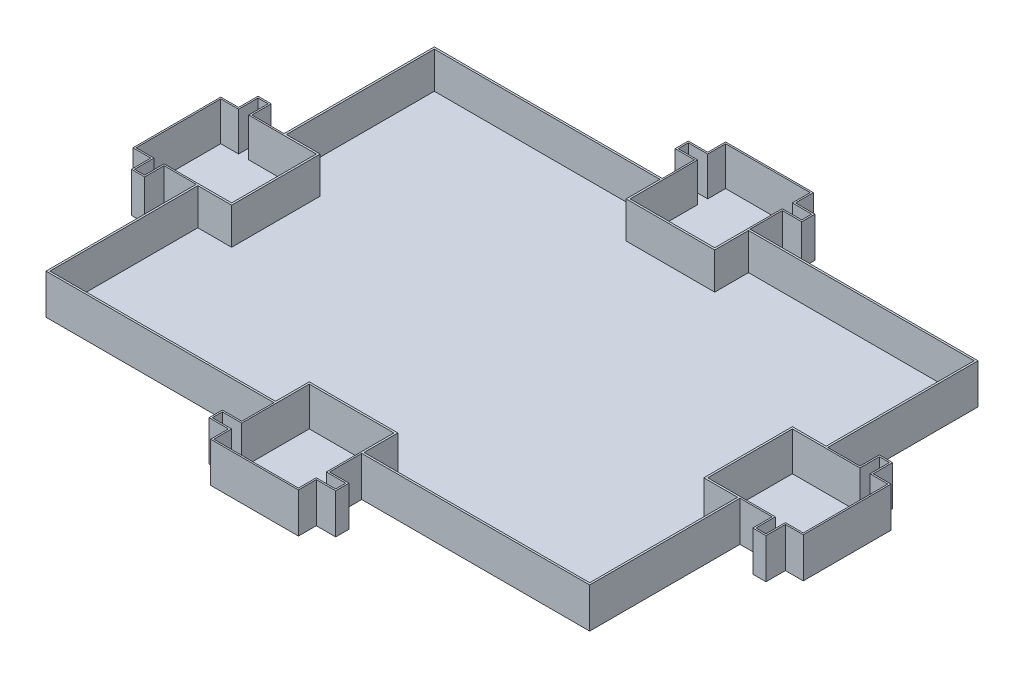
SolidWorks part; units mm, degrees
ref_plane "Alzado" through (0, 0, 0) normal (0, 0, 1) x (1, 0, 0)
ref_plane "Planta" through (0, 0, 0) normal (0, 1, 0) x (1, 0, 0)
ref_plane "Vista lateral" through (0, 0, 0) normal (1, 0, 0) x (0, 0, -1)
sketch "Croquis1" plane through (0, 0, 0) normal (0, 1, 0) x (1, 0, 0)
  line L0 (-10.9, -41.3) -> (10.9, -41.3)
  line L1 (70, -50) -> (-70, -50)
  line L2 (70, -50) -> (70, -10.9)
  line L3 (70, 50) -> (10.9, 50)
  line L4 (-70, -50) -> (-70, 50)
  line L5 (70, -50) -> (-70, 50) construction
  line L6 (70, 50) -> (-70, -50) construction
  line L11 (70, 10.9) -> (70, 50)
  line L12 (-78.3, 16.3) -> (-81.7, 16.3)
  line L13 (-10.9, -41.3) -> (-10.9, -58.7)
  line L15 (10.9, -41.3) -> (10.9, -58.7)
  line L16 (-81.7, 11.3) -> (-81.7, 16.3)
  line L17 (-81.7, 11.3) -> (-86.3, 11.3)
  line L19 (-10.9, 58.7) -> (-10.9, 41.3)
  line L20 (-10.9, 41.3) -> (10.9, 41.3)
  line L21 (10.9, 58.7) -> (10.9, 41.3)
  line L22 (-11.3, 58.3) -> (-11.3, 40.9)
  line L23 (-11.3, 40.9) -> (11.3, 40.9)
  line L24 (61.3, -10.9) -> (61.3, 10.9)
  line L25 (61.3, -10.9) -> (78.7, -10.9)
  line L27 (61.3, 10.9) -> (78.7, 10.9)
  line L28 (-86.3, 11.3) -> (-86.3, -11.3)
  line L29 (-81.7, -11.3) -> (-86.3, -11.3)
  line L32 (-10.9, -61.3) -> (-10.9, -65.9)
  line L33 (-10.9, -65.9) -> (10.9, -65.9)
  line L34 (10.9, -61.3) -> (10.9, -65.9)
  line L35 (-10.9, -58.7) -> (-15.9, -58.7)
  line L37 (-10.9, -61.3) -> (-15.9, -61.3)
  line L38 (-15.9, -58.7) -> (-15.9, -61.3)
  line L39 (10.9, -58.7) -> (15.9, -58.7)
  line L41 (10.9, -61.3) -> (15.9, -61.3)
  line L42 (15.9, -58.7) -> (15.9, -61.3)
  line L43 (0, 30.1645) -> (0, -22.5946)
  line L45 (-10.9, 61.3) -> (-10.9, 65.9)
  line L46 (-10.9, 65.9) -> (10.9, 65.9)
  line L47 (10.9, 61.3) -> (10.9, 65.9)
  line L48 (10.9, 58.7) -> (15.9, 58.7)
  line L50 (10.9, 61.3) -> (15.9, 61.3)
  line L51 (15.9, 58.7) -> (15.9, 61.3)
  line L52 (-10.9, 58.7) -> (-15.9, 58.7)
  line L54 (-10.9, 61.3) -> (-15.9, 61.3)
  line L55 (-15.9, 58.7) -> (-15.9, 61.3)
  line L56 (81.3, 10.9) -> (85.9, 10.9)
  line L58 (81.3, -10.9) -> (85.9, -10.9)
  line L59 (85.9, 10.9) -> (85.9, -10.9)
  line L61 (78.7, 10.9) -> (78.7, 15.9)
  line L62 (78.7, 15.9) -> (81.3, 15.9)
  line L63 (81.3, 10.9) -> (81.3, 15.9)
  line L65 (78.7, -10.9) -> (78.7, -15.9)
  line L66 (78.7, -15.9) -> (81.3, -15.9)
  line L67 (81.3, -10.9) -> (81.3, -15.9)
  line L68 (-78.7, 15.9) -> (-81.3, 15.9)
  line L69 (-78.7, 10.9) -> (-78.7, 15.9)
  line L70 (-81.3, 10.9) -> (-81.3, 15.9)
  line L71 (-81.7, -11.3) -> (-81.7, -16.3)
  line L72 (-81.3, 10.9) -> (-85.9, 10.9)
  line L73 (-85.9, 10.9) -> (-85.9, -10.9)
  line L74 (-78.7, -10.9) -> (-78.7, -15.9)
  line L75 (-81.3, -10.9) -> (-81.3, -15.9)
  line L76 (-78.7, -15.9) -> (-81.3, -15.9)
  line L77 (-81.3, -10.9) -> (-85.9, -10.9)
  line L78 (-61.3, -10.9) -> (-78.7, -10.9)
  line L79 (-61.3, -10.9) -> (-61.3, 10.9)
  line L80 (-61.3, 10.9) -> (-78.7, 10.9)
  line L81 (-78.3, -16.3) -> (-81.7, -16.3)
  line L82 (-78.3, -11.3) -> (-78.3, -16.3)
  line L83 (-60.9, -11.3) -> (-78.3, -11.3)
  line L84 (-60.9, -11.3) -> (-60.9, 11.3)
  line L85 (-60.9, 11.3) -> (-78.3, 11.3)
  line L86 (-78.3, 11.3) -> (-78.3, 16.3)
  line L87 (-10.9, 50) -> (-70, 50)
  line L88 (11.3, 58.3) -> (11.3, 40.9)
  line L89 (11.3, 58.3) -> (16.3, 58.3)
  line L90 (16.3, 58.3) -> (16.3, 61.7)
  line L91 (11.3, 61.7) -> (16.3, 61.7)
  line L92 (11.3, 61.7) -> (11.3, 66.3)
  line L93 (-11.3, 66.3) -> (11.3, 66.3)
  line L94 (-11.3, 61.7) -> (-11.3, 66.3)
  line L95 (-11.3, 61.7) -> (-16.3, 61.7)
  line L96 (-16.3, 58.3) -> (-16.3, 61.7)
  line L97 (-11.3, 58.3) -> (-16.3, 58.3)
  line L98 (81.7, 11.3) -> (86.3, 11.3)
  line L99 (86.3, 11.3) -> (86.3, -11.3)
  line L100 (81.7, -11.3) -> (86.3, -11.3)
  line L101 (81.7, -11.3) -> (81.7, -16.3)
  line L102 (78.3, -16.3) -> (81.7, -16.3)
  line L103 (78.3, -11.3) -> (78.3, -16.3)
  line L104 (60.9, -11.3) -> (78.3, -11.3)
  line L105 (60.9, -11.3) -> (60.9, 11.3)
  line L106 (60.9, 11.3) -> (78.3, 11.3)
  line L107 (78.3, 11.3) -> (78.3, 16.3)
  line L108 (78.3, 16.3) -> (81.7, 16.3)
  line L109 (81.7, 11.3) -> (81.7, 16.3)
  line L110 (-11.3, -40.9) -> (11.3, -40.9)
  line L111 (11.3, -40.9) -> (11.3, -58.3)
  line L112 (11.3, -58.3) -> (16.3, -58.3)
  line L113 (16.3, -58.3) -> (16.3, -61.7)
  line L114 (11.3, -61.7) -> (16.3, -61.7)
  line L115 (11.3, -61.7) -> (11.3, -66.3)
  line L116 (-11.3, -66.3) -> (11.3, -66.3)
  line L117 (-11.3, -61.7) -> (-11.3, -66.3)
  line L118 (-11.3, -61.7) -> (-16.3, -61.7)
  line L119 (-16.3, -58.3) -> (-16.3, -61.7)
  line L120 (-11.3, -58.3) -> (-16.3, -58.3)
  line L121 (-11.3, -40.9) -> (-11.3, -58.3)
  point P0 (0, 0)
  point P13 (0, -50)
  point P18 (0, 50)
  point P23 (70, 0)
  point P31 (0, -50)
  dimension "D1" = 140
  dimension "D2" = 100
  dimension "D3" = 0.4
  dimension "D4" = 0.4
  dimension "D5" = 21.8
  dimension "D6" = 17.4
  dimension "D7" = 21.8
  dimension "D8" = 17.4
  dimension "D9" = 21.8
  dimension "D10" = 17.4
  dimension "D11" = 2.6
  dimension "D12" = 5
  dimension "D13" = 2.6
  dimension "D14" = 5
  dimension "D15" = 21.8
  dimension "D16" = 4.6
  dimension "D17" = 5
  dimension "D18" = 2.6
  dimension "D19" = 4.6
  dimension "D20" = 21.8
  dimension "D21" = 2.6
  dimension "D22" = 21.8
  dimension "D23" = 4.6
  dimension "D24" = 5
  dimension "D25" = 5
  dimension "D26" = 0.4
  dimension "D27" = 0.4
extrude "Saliente-Extruir1" add sketch "Croquis1" against normal blind 10
shell "Vaciado2" thickness 0.5
sketch "Croquis4" plane through (0, -10, 0) normal (0, -1, 0) x (1, 0, 0)
  line L52 (-11.3, 50) -> (-70, 50)
  line L53 (-70, 50) -> (-70, 11.3)
  line L54 (-70, 11.3) -> (-78.3, 11.3)
  line L55 (-78.3, 11.3) -> (-78.3, 16.3)
  line L56 (-78.3, 16.3) -> (-81.7, 16.3)
  line L57 (-81.7, 16.3) -> (-81.7, 11.3)
  line L58 (-81.7, 11.3) -> (-86.3, 11.3)
  line L59 (-86.3, 11.3) -> (-86.3, -11.3)
  line L60 (-86.3, -11.3) -> (-81.7, -11.3)
  line L61 (-81.7, -11.3) -> (-81.7, -16.3)
  line L62 (-81.7, -16.3) -> (-78.3, -16.3)
  line L63 (-78.3, -16.3) -> (-78.3, -11.3)
  line L64 (-78.3, -11.3) -> (-70, -11.3)
  line L65 (-70, -11.3) -> (-70, -50)
  line L66 (-70, -50) -> (-11.3, -50)
  line L67 (-11.3, -50) -> (-11.3, -58.3)
  line L68 (-11.3, -58.3) -> (-16.3, -58.3)
  line L69 (-16.3, -58.3) -> (-16.3, -61.7)
  line L70 (-16.3, -61.7) -> (-11.3, -61.7)
  line L71 (-11.3, -61.7) -> (-11.3, -66.3)
  line L72 (-11.3, -66.3) -> (11.3, -66.3)
  line L73 (11.3, -66.3) -> (11.3, -61.7)
  line L74 (11.3, -61.7) -> (16.3, -61.7)
  line L75 (16.3, -61.7) -> (16.3, -58.3)
  line L76 (16.3, -58.3) -> (11.3, -58.3)
  line L77 (11.3, -58.3) -> (11.3, -50)
  line L78 (11.3, -50) -> (70, -50)
  line L79 (70, -50) -> (70, -11.3)
  line L80 (70, -11.3) -> (78.3, -11.3)
  line L81 (78.3, -11.3) -> (78.3, -16.3)
  line L82 (78.3, -16.3) -> (81.7, -16.3)
  line L83 (81.7, -16.3) -> (81.7, -11.3)
  line L84 (81.7, -11.3) -> (86.3, -11.3)
  line L85 (86.3, -11.3) -> (86.3, 11.3)
  line L86 (86.3, 11.3) -> (81.7, 11.3)
  line L87 (81.7, 11.3) -> (81.7, 16.3)
  line L88 (81.7, 16.3) -> (78.3, 16.3)
  line L89 (78.3, 16.3) -> (78.3, 11.3)
  line L90 (78.3, 11.3) -> (70, 11.3)
  line L91 (70, 11.3) -> (70, 50)
  line L92 (70, 50) -> (11.3, 50)
  line L93 (11.3, 50) -> (11.3, 58.3)
  line L94 (11.3, 58.3) -> (16.3, 58.3)
  line L95 (16.3, 58.3) -> (16.3, 61.7)
  line L96 (16.3, 61.7) -> (11.3, 61.7)
  line L97 (11.3, 61.7) -> (11.3, 66.3)
  line L98 (11.3, 66.3) -> (-11.3, 66.3)
  line L99 (-11.3, 66.3) -> (-11.3, 61.7)
  line L100 (-11.3, 61.7) -> (-16.3, 61.7)
  line L101 (-16.3, 61.7) -> (-16.3, 58.3)
  line L102 (-16.3, 58.3) -> (-11.3, 58.3)
  line L103 (-11.3, 58.3) -> (-11.3, 50)
  line L104 (-11.3, 50) -> (-70, 50)
  line L105 (-70, 50) -> (-70, 11.3)
  line L106 (-70, 11.3) -> (-78.3, 11.3)
  line L107 (-78.3, 11.3) -> (-78.3, 16.3)
  line L108 (-78.3, 16.3) -> (-81.7, 16.3)
  line L109 (-81.7, 16.3) -> (-81.7, 11.3)
  line L110 (-81.7, 11.3) -> (-86.3, 11.3)
  line L111 (-86.3, 11.3) -> (-86.3, -11.3)
  line L112 (-86.3, -11.3) -> (-81.7, -11.3)
  line L113 (-81.7, -11.3) -> (-81.7, -16.3)
  line L114 (-81.7, -16.3) -> (-78.3, -16.3)
  line L115 (-78.3, -16.3) -> (-78.3, -11.3)
  line L116 (-78.3, -11.3) -> (-70, -11.3)
  line L117 (-70, -11.3) -> (-70, -50)
  line L118 (-70, -50) -> (-11.3, -50)
  line L119 (-11.3, -50) -> (-11.3, -58.3)
  line L120 (-11.3, -58.3) -> (-16.3, -58.3)
  line L121 (-16.3, -58.3) -> (-16.3, -61.7)
  line L122 (-16.3, -61.7) -> (-11.3, -61.7)
  line L123 (-11.3, -61.7) -> (-11.3, -66.3)
  line L124 (-11.3, -66.3) -> (11.3, -66.3)
  line L125 (11.3, -66.3) -> (11.3, -61.7)
  line L126 (11.3, -61.7) -> (16.3, -61.7)
  line L127 (16.3, -61.7) -> (16.3, -58.3)
  line L128 (16.3, -58.3) -> (11.3, -58.3)
  line L129 (11.3, -58.3) -> (11.3, -50)
  line L130 (11.3, -50) -> (70, -50)
  line L131 (70, -50) -> (70, -11.3)
  line L132 (70, -11.3) -> (78.3, -11.3)
  line L133 (78.3, -11.3) -> (78.3, -16.3)
  line L134 (78.3, -16.3) -> (81.7, -16.3)
  line L135 (81.7, -16.3) -> (81.7, -11.3)
  line L136 (81.7, -11.3) -> (86.3, -11.3)
  line L137 (86.3, -11.3) -> (86.3, 11.3)
  line L138 (86.3, 11.3) -> (81.7, 11.3)
  line L139 (81.7, 11.3) -> (81.7, 16.3)
  line L140 (81.7, 16.3) -> (78.3, 16.3)
  line L141 (78.3, 16.3) -> (78.3, 11.3)
  line L142 (78.3, 11.3) -> (70, 11.3)
  line L143 (70, 11.3) -> (70, 50)
  line L144 (70, 50) -> (11.3, 50)
  line L145 (11.3, 50) -> (11.3, 58.3)
  line L146 (11.3, 58.3) -> (16.3, 58.3)
  line L147 (16.3, 58.3) -> (16.3, 61.7)
  line L148 (16.3, 61.7) -> (11.3, 61.7)
  line L149 (11.3, 61.7) -> (11.3, 66.3)
  line L150 (11.3, 66.3) -> (-11.3, 66.3)
  line L151 (-11.3, 66.3) -> (-11.3, 61.7)
  line L152 (-11.3, 61.7) -> (-16.3, 61.7)
  line L153 (-16.3, 61.7) -> (-16.3, 58.3)
  line L154 (-16.3, 58.3) -> (-11.3, 58.3)
  line L155 (-11.3, 58.3) -> (-11.3, 50)
  dimension "D1" = 0
extrude "Saliente-Extruir6" add sketch "Croquis4" along normal blind 0.3
